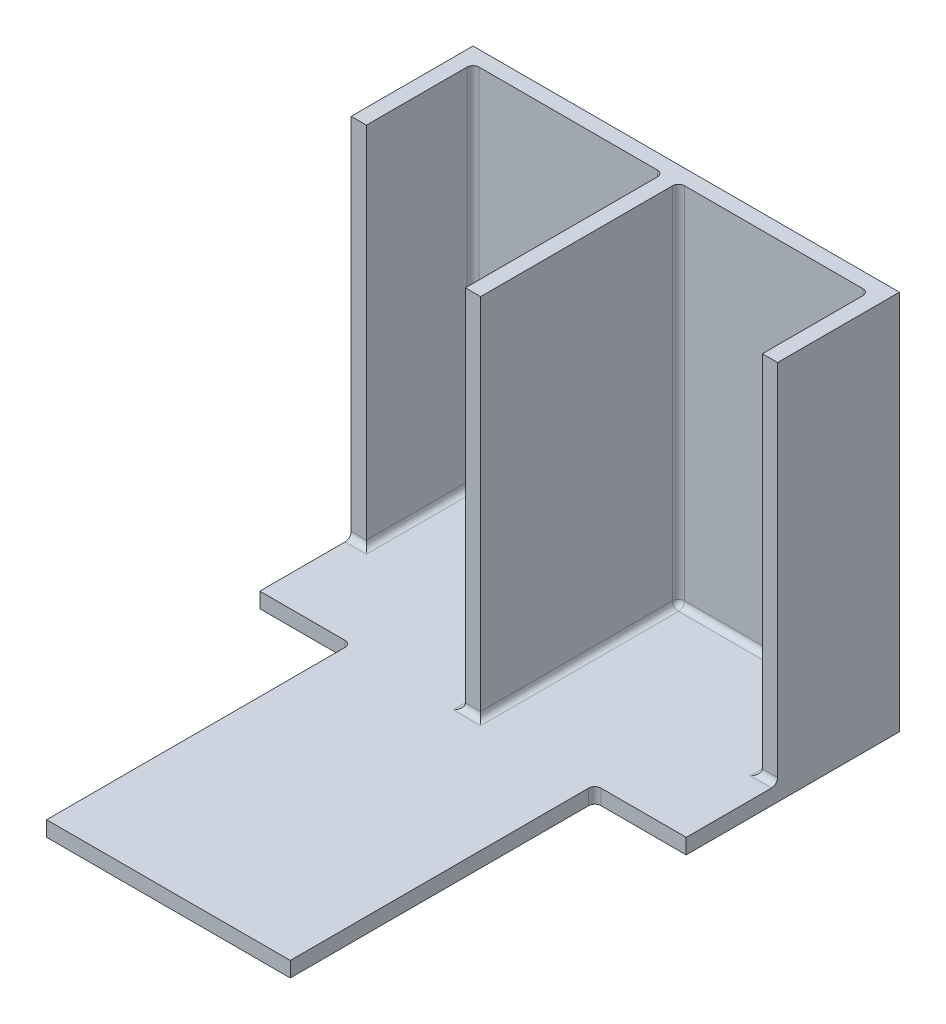
SolidWorks part; units mm, degrees
material "PBT General Purpose"
ref_plane "Front Plane" through (0, 0, 0) normal (0, 0, 1) x (1, 0, 0)
ref_plane "Top Plane" through (0, 0, 0) normal (0, 1, 0) x (1, 0, 0)
ref_plane "Right Plane" through (0, 0, 0) normal (1, 0, 0) x (0, 0, -1)
sketch "Sketch1" plane through (0, 0, 0) normal (0, 1, 0) x (1, 0, 0)
  line L0 (20, -17.5) -> (35, -17.5)
  line L1 (-35, -17.5) -> (-20, -17.5)
  line L2 (-35, -17.5) -> (-35, 17.5)
  line L3 (-35, 17.5) -> (35, 17.5)
  line L4 (35, -17.5) -> (35, 17.5)
  line L5 (-35, -17.5) -> (35, 17.5) construction
  line L6 (-35, 17.5) -> (35, -17.5) construction
  line L8 (20, -17.5) -> (20, -67.5)
  line L9 (20, -67.5) -> (-20, -67.5)
  line L10 (-20, -17.5) -> (-20, -67.5)
  point P0 (0, 0)
  dimension "D1" = 70
  dimension "D2" = 35
  dimension "D3" = 50
  dimension "D4" = 40
extrude "Boss-Extrude1" add sketch "Sketch1" along normal blind 2.5
sketch "Sketch3" plane through (0, 2.5, 0) normal (0, 1, 0) x (1, 0, 0)
  line L0 (0, 15) -> (0, 17.5) construction
  line L1 (-35, 17.5) -> (-32.5, 17.5)
  line L2 (-35, 17.5) -> (-35, -2.5)
  line L3 (-35, -2.5) -> (-32.5, -2.5)
  line L4 (-32.5, 15) -> (-32.5, -2.5)
  line L5 (35, 17.5) -> (32.5, 17.5)
  line L6 (35, 17.5) -> (35, -2.5)
  line L7 (35, -2.5) -> (32.5, -2.5)
  line L8 (32.5, 15) -> (32.5, -2.5)
  line L9 (32.5, 17.5) -> (-32.5, 17.5)
  line L11 (32.5, 15) -> (1.25, 15)
  line L13 (-1.25, 15) -> (-32.5, 15)
  line L14 (-1.25, -17.5) -> (1.25, -17.5)
  line L15 (-1.25, -17.5) -> (-1.25, 15)
  line L17 (1.25, -17.5) -> (1.25, 15)
  line L18 (1.25, 15) -> (-1.25, 15) construction
  line L19 (-35, -17.5) -> (-20, -17.5) construction
  point P18 (0, 15)
  dimension "D1" = 2.5
  dimension "D2" = 20
extrude "Boss-Extrude2" add sketch "Sketch3" along normal blind 60
fillet "Fillet1" radius 1 15 edges at (-20, 1.25, 17.5) (20, 1.25, 17.5) (-33.75, 2.5, 2.5) (-32.5, 32.5, -15) (-32.5, 2.5, -6.25) (-1.25, 32.5, -15) (-16.875, 2.5, -15) (-1.25, 2.5, 1.25) (33.75, 2.5, 2.5) (0, 2.5, 17.5) (1.25, 2.5, 1.25) (1.25, 32.5, -15) (16.875, 2.5, -15) (32.5, 32.5, -15) (32.5, 2.5, -6.25)
